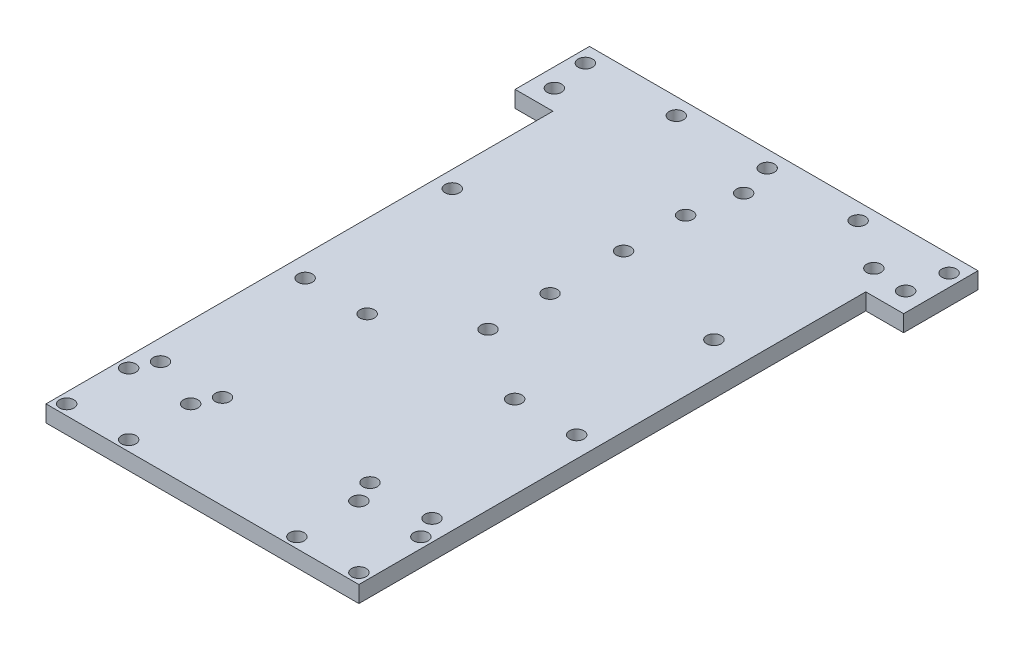
SolidWorks part; units mm, degrees
ref_plane "Front Plane" through (0, 0, 0) normal (0, 0, 1) x (1, 0, 0)
ref_plane "Top Plane" through (0, 0, 0) normal (0, 1, 0) x (1, 0, 0)
ref_plane "Right Plane" through (0, 0, 0) normal (1, 0, 0) x (0, 0, -1)
sketch "Sketch1" plane through (0, 0, 0) normal (0, 1, 0) x (1, 0, 0)
  line L1 (-37.85, 21.35) -> (37.85, 21.35)
  line L2 (-37.85, 21.35) -> (-37.85, -21.35)
  line L3 (-37.85, -21.35) -> (37.85, -21.35)
  line L4 (37.85, 21.35) -> (37.85, -21.35)
  line L5 (-37.85, 21.35) -> (37.85, -21.35) construction
  line L6 (-37.85, -21.35) -> (37.85, 21.35) construction
  circle A0 centre (2.4, 17.25) radius 1.75
  circle A1 centre (-33.8, -17.05) radius 1.75
  circle A2 centre (29.5, -17.05) radius 1.75
  circle A3 centre (33.9, 17.25) radius 1.75
  point P0 (0, 0)
  dimension "D9" = 3.5
  dimension "D1" = 75.7
  dimension "D2" = 42.7
  dimension "D3" = 4.1
  dimension "D4" = 4.3
  dimension "D5" = 4.05
  dimension "D6" = 8.35
  dimension "D7" = 3.95
  dimension "D8" = 40.25
extrude "Boss-Extrude1" add sketch "Sketch1" along normal blind 4
sketch "Sketch3" plane through (0, 4, 0) normal (0, 1, 0) x (1, 0, 0)
  line L0 (0, 0) -> (-31.55, 0) construction
  line L1 (-2.2, 0) -> (2.2, 0) construction
  line L2 (-31.55, 0) -> (-31.55, 14.5) construction
  line L3 (-31.55, 14.5) -> (27.25, 14.5) construction
  line L4 (27.25, 14.5) -> (27.25, -51.1) construction
  line L5 (27.25, -51.1) -> (-31.55, -51.1) construction
  line L6 (-31.55, -51.1) -> (-31.55, 0) construction
  line L7 (0, 14.5) -> (0, -51.1) construction
  line L8 (0, -2.2) -> (0, 2.2) construction
  line L9 (-31.55, -18.3) -> (27.25, -18.3) construction
  line L10 (-37.85, -21.35) -> (-37.85, -51.1)
  line L11 (37.85, -21.35) -> (37.85, -51.1)
  line L12 (37.85, -51.1) -> (-37.85, -51.1)
  line L13 (-37.85, -21.35) -> (37.85, -21.35)
  circle A0 centre (0, 5.6) radius 1.75
  circle A1 centre (0, -9.4) radius 1.75
  circle A2 centre (0, -27.2) radius 1.75
  circle A3 centre (0, -42.2) radius 1.75
  line M18 (-37.85, -21.35) -> (37.85, -21.35)
  dimension "D10" = 3.5
  dimension "D1" = 58.8
  dimension "D2" = 31.55
  dimension "D3" = 65.6
  dimension "D4" = 14.5
  dimension "D5" = 32.8
  dimension "D6" = 15
  dimension "D7" = 15
  dimension "D8" = 8.9
  dimension "D9" = 8.9
extrude "Boss-Extrude2" add sketch "Sketch3" against normal blind 4 contours L12 L11 L10 A3 A2 M18 region at (0, 4, 36.2381)
extrude "Cut-Extrude1" cut sketch "Sketch3<3>" against normal blind 4 contours A0 | A1
sketch "Sketch3<3>" plane through (0, 4, 0) normal (0, 1, 0) x (1, 0, 0) same geometry as "Sketch3"
sketch "Sketch4" plane through (0, 0, 0) normal (0, 1, 0) x (1, 0, 0)
  line L0 (-37.85, -51.1) -> (-37.85, -91.1) construction
  line L1 (-37.85, -91.1) -> (37.85, -91.1) construction
  line L2 (37.85, 21.35) -> (44, 21.35) construction
  line L3 (44, 21.35) -> (44, 29.35) construction
  line L4 (-37.85, 21.35) -> (-44, 21.35) construction
  line L6 (37.85, -51.1) -> (37.85, -91.1) construction
  line L7 (-44, 21.35) -> (-44, 29.35) construction
  line L8 (-44, 29.35) -> (44, 29.35) construction
  line L10 (-37.85, -51.1) -> (-37.85, -91.1)
  line L11 (-37.85, -91.1) -> (37.85, -91.1)
  line L12 (37.85, -91.1) -> (37.85, -51.1)
  line L13 (37.85, -51.1) -> (-37.85, -51.1)
  line L14 (-37.85, 21.35) -> (-44, 21.35)
  line L15 (-44, 21.35) -> (-44, 29.35)
  line L16 (-44, 29.35) -> (44, 29.35)
  line L17 (44, 29.35) -> (44, 21.35)
  line L18 (44, 21.35) -> (37.85, 21.35)
  line L19 (37.85, 21.35) -> (-37.85, 21.35)
  line L20 (0, -2.2) -> (0, 2.2) construction
  circle A0 centre (-32.85, -53.6) radius 1.75
  circle A1 centre (-17.85, -53.6) radius 1.75
  circle A2 centre (-17.85, -88.6) radius 1.75
  circle A3 centre (-32.85, -88.6) radius 1.75
  circle A4 centre (32.85, -88.6) radius 1.75
  circle A5 centre (17.85, -88.6) radius 1.75
  circle A6 centre (17.85, -53.6) radius 1.75
  circle A7 centre (32.85, -53.6) radius 1.75
  dimension "D5" = 3.5
  dimension "D1" = 88
  dimension "D2" = 8
  dimension "D3" = 40
  dimension "D4" = 6.15
  dimension "D6" = 15
  dimension "D7" = 5
  dimension "D8" = 2.5
  dimension "D9" = 2.5
extrude "Boss-Extrude3" add sketch "Sketch4" along normal blind 4
sketch "Sketch6" plane through (0, 4, 0) normal (0, 1, 0) x (1, 0, 0)
  line L0 (-44, 25.35) -> (44, 25.35) construction
  line L1 (-44, 29.35) -> (-44, 21.35) construction
  line L2 (44, 21.35) -> (44, 29.35) construction
  line L3 (-44, 29.35) -> (-47, 29.35)
  line L4 (-47, 29.35) -> (-47, 21.35)
  line L5 (-47, 21.35) -> (-44, 21.35)
  line L6 (44, 29.35) -> (47, 29.35)
  line L7 (47, 29.35) -> (47, 21.35)
  line L8 (47, 21.35) -> (44, 21.35)
  line L9 (44, 21.35) -> (44, 23.6)
  line L10 (44, 29.35) -> (44, 27.1)
  line L11 (-44, 21.35) -> (-44, 23.6)
  line L12 (-44, 29.35) -> (-44, 27.1)
  circle A0 centre (0, 25.35) radius 1.75
  circle A1 centre (22, 25.35) radius 1.75
  circle A2 centre (44, 25.35) radius 1.75
  circle A3 centre (-22, 25.35) radius 1.75
  circle A4 centre (-44, 25.35) radius 1.75
  line M16 (44, 21.35) -> (44, 29.35)
  line M18 (-44, 29.35) -> (-44, 21.35)
  dimension "D5" = 3.5
  dimension "D1" = 22
  dimension "D2" = 22
  dimension "D3" = 22
  dimension "D4" = 22
  dimension "D6" = 3
  dimension "D7" = 3
extrude "Boss-Extrude4" add sketch "Sketch6" against normal blind 4 contours A4 L3 L4 L5 M18 | A2 L8 L7 L6 M16 region at (-44.0854, 4, -28.225) region at (45.5, 4, -29.2646)
extrude "Cut-Extrude2" cut sketch "Sketch6<3>" against normal through all contours A4 | A3 | A1 | A2 | A0
sketch "Sketch6<3>" plane through (0, 4, 0) normal (0, 1, 0) x (1, 0, 0) same geometry as "Sketch6"
sketch "Sketch7" plane through (0, 0, 0) normal (0, 1, 0) x (1, 0, 0)
  line L0 (-47, 21.35) -> (-47, 11.35)
  line L1 (-47, 11.35) -> (-37.85, 11.35)
  line L2 (-37.85, 21.35) -> (-37.85, -91.1) construction
  line L3 (-37.85, 11.35) -> (-37.85, 21.35)
  line L4 (-37.85, 21.35) -> (-47, 21.35)
  line L5 (47, 21.35) -> (47, 11.35)
  line L6 (47, 11.35) -> (37.85, 11.35)
  line L7 (37.85, -91.1) -> (37.85, 21.35) construction
  line L8 (37.85, 11.35) -> (37.85, 21.35)
  line L9 (37.85, 21.35) -> (47, 21.35)
  circle A0 centre (-42.5, 16.35) radius 1.75
  circle A1 centre (42.5, 16.35) radius 1.75
  dimension "D6" = 3.5
  dimension "D1" = 10
  dimension "D2" = 10
  dimension "D3" = 4.5
  dimension "D4" = 4.5
  dimension "D5" = 5
extrude "Boss-Extrude5" add sketch "Sketch7" along normal blind 4
sketch "Sketch8" plane through (0, 0, 0) normal (0, 1, 0) x (1, 0, 0)
  line L0 (-37.85, -91.1) -> (-37.85, -111.3)
  line L1 (-37.85, -111.3) -> (37.85, -111.3)
  line L2 (37.85, -111.3) -> (37.85, -91.1)
  line L3 (-37.85, -91.1) -> (37.85, -91.1)
  dimension "D1" = 20.2
extrude "Boss-Extrude6" add sketch "Sketch8" along normal blind 4
sketch "Sketch9" plane through (0, 4, 0) normal (0, 1, 0) x (1, 0, 0)
  line L0 (-37.85, -111.3) -> (-17.85, -111.3) construction
  line L1 (-37.85, -111.3) -> (37.85, -111.3) construction
  line L2 (-17.85, -111.3) -> (-17.85, -91.3) construction
  line L3 (-17.85, -91.3) -> (-37.85, -91.3) construction
  line L4 (-37.85, 11.35) -> (-37.85, -111.3) construction
  line L5 (-37.85, -91.3) -> (-37.85, -111.3) construction
  circle A0 centre (-35.35, -93.8) radius 1.75
  circle A1 centre (-20.35, -93.8) radius 1.75
  circle A2 centre (-20.35, -108.8) radius 1.75
  circle A3 centre (-35.35, -108.8) radius 1.75
  point P17 (0, 0)
  point P18 (0, 0)
  point P19 (0, 0)
  point P20 (0, 0)
  point P21 (0, 0)
  dimension "D7" = 3.5
  dimension "D1" = 20
  dimension "D2" = 20
  dimension "D3" = 2.5
  dimension "D4" = 2.5
  dimension "D5" = 2.5
  dimension "D6" = 2.5
extrude "Cut-Extrude3" cut sketch "Sketch9" against normal through all
mirror "Mirror1" about plane through (0, 0, 0) normal (1, 0, 0) of "Cut-Extrude3"
